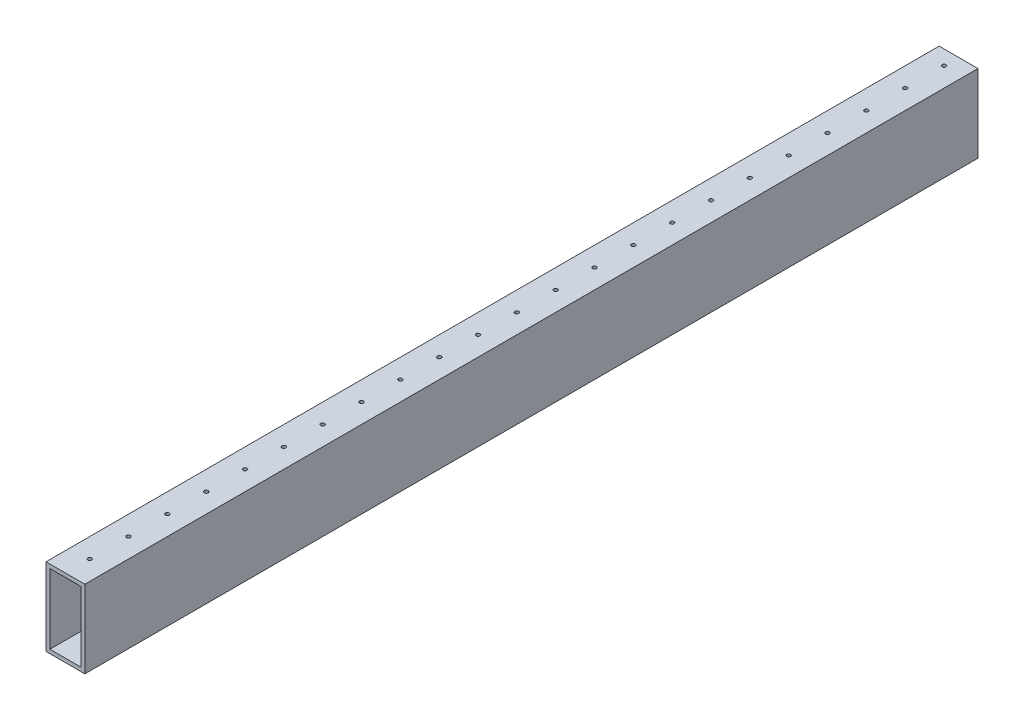
SolidWorks part; units mm, degrees
material "1060 Alloy"
ref_plane "Front Plane" through (0, 0, 0) normal (0, 0, 1) x (1, 0, 0)
ref_plane "Top Plane" through (0, 0, 0) normal (0, 1, 0) x (1, 0, 0)
ref_plane "Right Plane" through (0, 0, 0) normal (1, 0, 0) x (0, 0, -1)
sketch "Sketch1" plane through (0, 0, 0) normal (0, 0, 1) x (1, 0, 0)
  line L1 (-12.7, -25.4) -> (12.7, -25.4)
  line L2 (-12.7, -25.4) -> (-12.7, 25.4)
  line L3 (-12.7, 25.4) -> (12.7, 25.4)
  line L4 (12.7, -25.4) -> (12.7, 25.4)
  point P5 (-12.7, 0)
  point P7 (0, 25.4)
  dimension "D1" = 50.8
  dimension "D2" = 25.4
extrude "Extrude-Thin1" add sketch "Sketch1" along normal mid plane 584.2 thin thin type one direction reverse wall 2.54
sketch "Sketch2" plane through (0, 25.4, 0) normal (0, 1, 0) x (1, 0, 0)
  line L0 (12.7, 292.1) -> (-12.7, 292.1) construction
  circle A0 centre (0, 282.575) radius 1.27
  point P5 (0, 292.1)
  dimension "D1" = 2.54
  dimension "D2" = 9.525
extrude "Cut-Extrude1" cut sketch "Sketch2" against normal through all
pattern_linear "LPattern1" count 23 spacing 25.4 along (0, 0, 1) of "Cut-Extrude1"
sketch "Sketch4" [suppressed] plane through (-12.7, 0, 0) normal (-1, 0, 0) x (0, 0, 1)
  line L0 (263.906, 1.651) -> (272.796, 1.651) construction
  line L1 (263.906, 8.509) -> (272.796, 8.509)
  line L2 (263.906, -5.207) -> (272.796, -5.207)
  line L3 (-263.906, 1.651) -> (-222.25, 1.651) construction
  line L4 (0, 25.4) -> (0, -25.4) construction
  line L5 (379.4125, 25.4) -> (-379.4125, 25.4) construction
  line L6 (379.4125, -25.4) -> (-379.4125, -25.4) construction
  line L9 (-263.906, 1.651) -> (-272.796, 1.651) construction
  line L10 (-263.906, 8.509) -> (-272.796, 8.509)
  line L11 (-263.906, -5.207) -> (-272.796, -5.207)
  circle A3 centre (0, 1.651) radius 19.05
  arc A6 (-263.906, 8.509) -> (-263.906, -5.207) centre (-263.906, 1.651) cw
  arc A7 (-272.796, -5.207) -> (-272.796, 8.509) centre (-272.796, 1.651) cw
  circle A8 centre (-222.25, 1.651) radius 1.9304
  arc A12 (263.906, 8.509) -> (263.906, -5.207) centre (263.906, 1.651) ccw
  arc A13 (272.796, -5.207) -> (272.796, 8.509) centre (272.796, 1.651) ccw
  circle A14 centre (222.25, 1.651) radius 1.9304
  point P3 (268.351, 1.651)
  point P27 (-268.351, 1.651)
  dimension "D1" = 222.25
  dimension "D4" = 38.1
  dimension "D5" = 6.858
  dimension "D7" = 41.656
  dimension "D6" = 3.8608
  dimension "D2" = 1.651
  dimension "D8" = 8.89
extrude "Cut-Extrude2" [suppressed] cut sketch "Sketch4" against normal through all
sketch "Sketch5" [suppressed] plane through (-12.7, 0, 0) normal (-1, 0, 0) x (0, 0, 1)
  line L0 (-44.45, 14.351) -> (44.45, -11.049) construction
  line L1 (0, -17.399) -> (0, 20.701) construction
  circle A0 centre (0, 1.651) radius 19.05 construction
  circle A12 centre (-44.45, 14.351) radius 3.175
  circle A13 centre (-44.45, -11.049) radius 3.175
  circle A14 centre (44.45, 14.351) radius 3.175
  circle A15 centre (44.45, -11.049) radius 3.175
  point P7 (0, 1.651)
  point P12 (0, 1.651)
  dimension "D1" = 25.4
  dimension "D2" = 88.9
  dimension "D3" = 6.35
extrude "Cut-Extrude3" [suppressed] cut sketch "Sketch5" against normal through all
